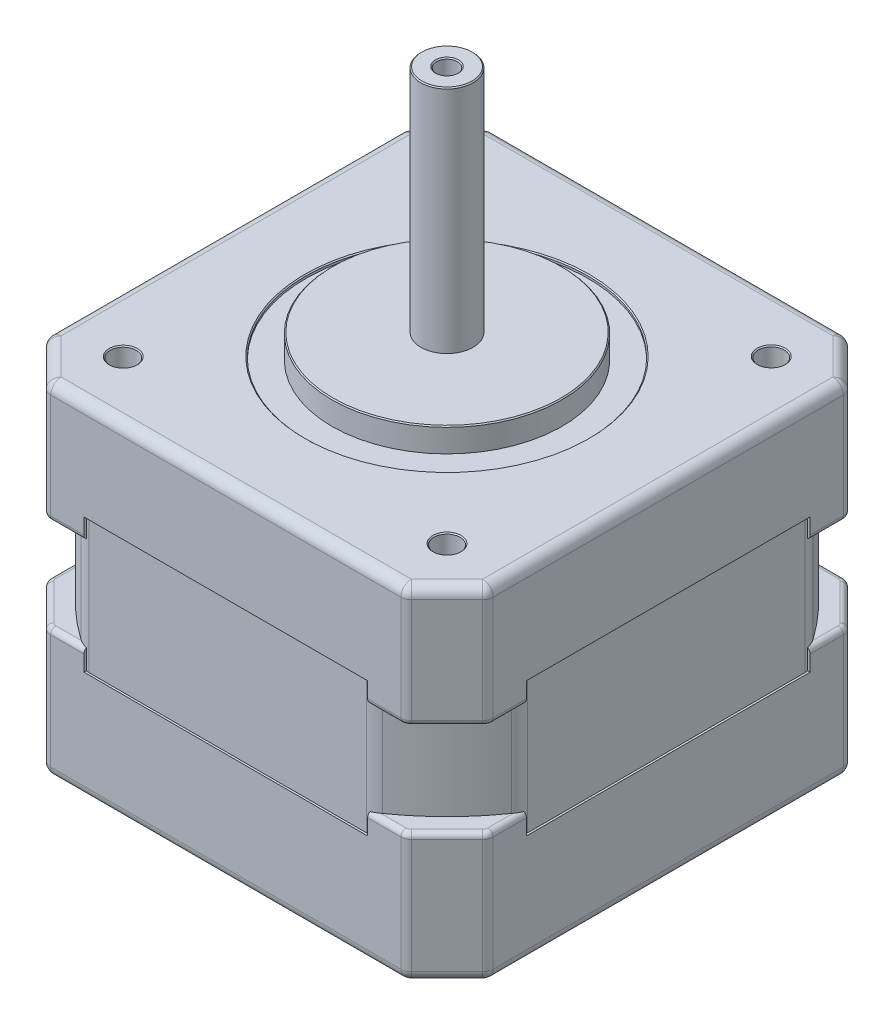
SolidWorks part; units mm, degrees
ref_plane "Front Plane" through (0, 0, 0) normal (0, 0, 1) x (1, 0, 0)
ref_plane "Top Plane" through (0, 0, 0) normal (0, 1, 0) x (1, 0, 0)
ref_plane "Right Plane" through (0, 0, 0) normal (1, 0, 0) x (0, 0, -1)
sketch "Sketch1" plane through (0, 0, 0) normal (0, 1, 0) x (1, 0, 0)
  line L0 (0, 21.15) -> (0, 0) construction
  line L1 (-21.15, 21.15) -> (-21.15, -21.15)
  line L2 (-21.15, -21.15) -> (21.15, -21.15)
  line L3 (-21.15, 21.15) -> (21.15, 21.15)
  line L4 (21.15, -21.15) -> (21.15, 21.15)
  line L5 (21.15, 0) -> (0, 0) construction
  line L6 (21.15, 21.15) -> (0, 0) construction
  circle A0 centre (15.5, 15.5) radius 1.25
  circle A1 centre (-15.4497, 15.5) radius 1.25
  circle A2 centre (-15.4497, -15.5) radius 1.25
  circle A3 centre (15.5, -15.5) radius 1.25
  dimension "D1" = 42.3
  dimension "D3" = 2.5
  dimension "D2" = 31
extrude "Boss-Extrude1" add sketch "Sketch1" against normal blind 32.8
chamfer "Chamfer1" distance 4 angle 45 4 edges at (21.15, -16.4, 21.15) (-21.15, -16.4, 21.15) (-21.15, -16.4, -21.15) (21.15, -16.4, -21.15)
sketch "Sketch2" plane through (0, 0, 0) normal (0, 1, 0) x (1, 0, 0)
  circle A0 centre (0, 0) radius 11
  dimension "D1" = 22
extrude "Boss-Extrude2" add sketch "Sketch2" along normal blind 2
sketch "Sketch6" plane through (0, -32.8, 0) normal (0, -1, 0) x (1, 0, 0)
  line L0 (-17.15, 21.15) -> (17.15, 21.15) construction
  line L1 (-21.15, -17.15) -> (-21.15, 17.15) construction
  line L2 (-17.15, 21.15) -> (-21.15, 17.15) construction
  line L3 (-17.15, 21.15) -> (-21.15, 17.15)
  line L4 (-21.15, 13.5626) -> (-21.15, 17.15)
  line L5 (-17.15, 21.15) -> (-13.5626, 21.15)
  arc A0 (-13.5626, 21.15) -> (-21.15, 13.5626) centre (0, 0) ccw
  dimension "D1" = 25.125
extrude "Cut-Extrude2" cut sketch "Sketch6" against normal offset from surface (8.85 mm away) 11.5 from offset 12.45 up to face at (0, 0, 0) offset against normal yes
pattern_circular "CirPattern1" count 4 over 360 about axis through (0, 10.7303, 0) along (0, -1, 0) of "Cut-Extrude2"
sketch "Sketch7" plane through (-21.15, 0, 0) normal (-1, 0, 0) x (0, 0, 1)
  line L0 (13.5626, -11.5) -> (13.5626, -20.35) construction
  line L1 (-13.5626, -9.5) -> (13.5626, -9.5)
  line L2 (-13.5626, -9.5) -> (-13.5626, -11.5)
  line L3 (-13.5626, -22.35) -> (13.5626, -22.35)
  line L4 (13.5626, -9.5) -> (13.5626, -11.5)
  line L5 (-13.5626, -11.5) -> (-13.5626, -20.35) construction
  line L6 (-17.15, -11.5) -> (-13.5626, -11.5) construction
  line L7 (-13.5626, -20.35) -> (-17.15, -20.35) construction
  line L8 (-21.15, -11.5) -> (-13.5626, -11.5) construction
  line L9 (-17.3563, -11.5) -> (-13.5626, -11.5)
  line L10 (-17.3563, -11.5) -> (-17.3563, -20.35)
  line L11 (-17.3563, -20.35) -> (-13.5626, -20.35)
  line L12 (19.15, -11.5) -> (19.15, -20.35)
  line L13 (21.15, -20.35) -> (17.15, -20.35) construction
  line L14 (13.5626, -11.5) -> (19.15, -11.5)
  line L15 (-13.5626, -20.35) -> (-13.5626, -22.35)
  line L16 (13.5626, -20.35) -> (13.5626, -22.35)
  line L17 (13.5626, -20.35) -> (19.15, -20.35)
  dimension "D1" = 2
  dimension "D2" = 2
extrude "Cut-Extrude3" cut sketch "Sketch7" against normal blind 0.2
pattern_circular "CirPattern2" count 4 over 360 about axis through (0, 2, 0) along (0, -1, 0) of "Cut-Extrude3"
sketch "Sketch3" plane through (0, 0, 0) normal (0, 1, 0) x (1, 0, 0)
  circle A0 centre (0, 0) radius 2.5
  dimension "D1" = 5
extrude "Boss-Extrude3" add sketch "Sketch3" along normal blind 24
sketch "Sketch8" plane through (0, -32.8, 0) normal (0, -1, 0) x (1, 0, 0)
  circle A0 centre (15.5, -15.5) radius 3.075
  circle A1 centre (15.5, 15.5) radius 3.075
  circle A2 centre (-15.4497, 15.5) radius 3.075
  circle A3 centre (-15.4497, -15.5) radius 3.075
  dimension "D1" = 6.15
extrude "Cut-Extrude4" cut sketch "Sketch8" against normal blind 2
sketch "Sketch9" plane through (0, -32.8, 0) normal (0, -1, 0) x (1, 0, 0)
  circle A0 centre (0, 0) radius 4.625
  dimension "D1" = 9.25
extrude "Cut-Extrude5" cut sketch "Sketch9" against normal blind 3
sketch "Sketch10" plane through (0, 0, -21.15) normal (0, 0, -1) x (-1, 0, 0)
  line L0 (-13.5626, -22.35) -> (13.5626, -22.35) construction
  line L1 (-4.1, -30.55) -> (4.1, -30.55)
  line L2 (-4.1, -30.55) -> (-4.1, -22.35)
  line L3 (-4.1, -22.35) -> (4.1, -22.35)
  line L4 (4.1, -30.55) -> (4.1, -22.35)
  line L5 (-4.1, -30.55) -> (4.1, -22.35) construction
  line L6 (-4.1, -22.35) -> (4.1, -30.55) construction
  line L7 (0, -11.5) -> (0, -20.35) construction
  point P0 (0, -26.45)
  dimension "D1" = 8.2
extrude "Cut-Extrude6" cut sketch "Sketch10" against normal blind 0.5
sketch "Sketch11" plane through (0, 0, 0) normal (0, 1, 0) x (1, 0, 0)
  circle A0 centre (0, 0) radius 11 construction
  circle A1 centre (0, 0) radius 11
  circle A2 centre (0, 0) radius 13.5
  dimension "D1" = 2.5
extrude "Cut-Extrude7" cut sketch "Sketch11" against normal blind 0.3
fillet "Fillet2" radius 2 8 edges at (-13.8695, -15.925, -20.95) (13.8695, -15.925, -20.95) (20.95, -15.925, -13.8695) (20.95, -15.925, 13.8695) (13.8695, -15.925, 20.95) (-13.8695, -15.925, 20.95) (-20.95, -15.925, 13.8695) (-20.95, -15.925, -13.8695)
fillet "Fillet1" radius 1 32 edges at (0, 0, 21.15) (0, -32.8, 21.15) (19.15, 0, -19.15) (19.15, -32.8, -19.15) (17.15, -5.75, -21.15) (17.15, -26.575, -21.15) (0, 0, -21.15) (0, -32.8, -21.15) (-17.15, -5.75, -21.15) (-17.15, -26.575, -21.15) (-19.15, 0, -19.15) (-19.15, -32.8, -19.15) (-21.15, -5.75, -17.15) (-21.15, -26.575, -17.15) (-21.15, 0, 0) (-21.15, -32.8, 0) (-21.15, -5.75, 17.15) (-21.15, -26.575, 17.15) (-19.15, 0, 19.15) (-17.15, -5.75, 21.15) (-17.15, -26.575, 21.15) (-19.15, -32.8, 19.15) (21.15, -5.75, -17.15) (21.15, -26.575, -17.15) (21.15, -32.8, 0) (21.15, 0, 0) (17.15, -5.75, 21.15) (17.15, -26.575, 21.15) (19.15, 0, 19.15) (21.15, -5.75, 17.15) (21.15, -26.575, 17.15) (19.15, -32.8, 19.15)
fillet "Fillet3" radius 0.5 40 edges at (21.15, -11.5, -15.1492) (21.0739, -11.5, -17.1185) (15.1492, -11.5, -21.15) (17.1185, -11.5, -21.0739) (15.1492, -20.35, -21.15) (17.1185, -20.35, -21.0739) (19.15, -20.35, -19.15) (21.0739, -20.35, -17.1185) (15.1492, -11.5, 21.15) (17.1185, -11.5, 21.0739) (21.15, -11.5, 15.1492) (21.0739, -11.5, 17.1185) (21.15, -20.35, 15.1492) (21.0739, -20.35, 17.1185) (15.1492, -20.35, 21.15) (17.1185, -20.35, 21.0739) (-21.15, -20.35, -15.1492) (-21.0739, -20.35, -17.1185) (-15.1492, -20.35, -21.15) (-17.1185, -20.35, -21.0739) (-15.1492, -20.35, 21.15) (-17.1185, -20.35, 21.0739) (-21.15, -20.35, 15.1492) (-21.0739, -20.35, 17.1185) (-21.15, -11.5, 15.1492) (-21.0739, -11.5, 17.1185) (-15.1492, -11.5, 21.15) (-17.1185, -11.5, 21.0739) (-15.1492, -11.5, -21.15) (-17.1185, -11.5, -21.0739) (-21.15, -11.5, -15.1492) (-21.0739, -11.5, -17.1185) (19.15, -11.5, -19.15) (21.15, -20.35, -15.1492) (19.15, -11.5, 19.15) (19.15, -20.35, 19.15) (-19.15, -20.35, -19.15) (-19.15, -20.35, 19.15) (-19.15, -11.5, 19.15) (-19.15, -11.5, -19.15)
chamfer "Chamfer2" distance 0.1 angle 45 6 edges at (0, 2, 11) (0, 0, 13.5) (-15.4497, 0, 16.75) (-15.4497, 0, -14.25) (15.5, 0, -14.25) (15.5, 0, 16.75)
sketch "Sketch12" plane through (0, 24, 0) normal (0, 1, 0) x (1, 0, 0)
  circle A0 centre (0, 0) radius 1
  dimension "D1" = 2
extrude "Cut-Extrude8" cut sketch "Sketch12" against normal blind 2.5
chamfer "Chamfer3" distance 0.1 angle 45 2 edges at (0, 24, 2.5) (0, 24, 1)
chamfer "Chamfer4" distance 0.3 angle 45 5 edges at (15.5, -32.8, -18.575) (15.5, -32.8, 12.425) (-15.4497, -32.8, 12.425) (-15.4497, -32.8, -18.575) (0, -32.8, -4.625)
sketch "Sketch13" plane through (0, 0, -20.65) normal (0, 0, -1) x (-1, 0, 0)
  line L0 (-2.025, -29.05) -> (2.025, -29.05) construction
  line L4 (-4.1, -30.55) -> (4.1, -30.55) construction
  line L8 (0, -29.8) -> (0, -32.5) construction
  circle A0 centre (-2.025, -29.05) radius 0.65
  circle A1 centre (-0.675, -29.05) radius 0.65
  circle A2 centre (0.675, -29.05) radius 0.65
  circle A3 centre (2.025, -29.05) radius 0.65
  point P8 (0, -29.05)
  dimension "D1" = 1.3
  dimension "D3" = 1.35
  dimension "D2" = 1.5
  dimension "D4" = 1.35
  dimension "D5" = 1.35
extrude "Boss-Extrude5" add sketch "Sketch13" along normal blind 5.5
sketch "Sketch5" plane through (-12.85, -32.8, 0) normal (0, 1, 0) x (0, 0, -1)
  line L0 (-20.15, -7.0234) -> (20.15, -7.0234) construction
  line L1 (20.15, 3.8858) -> (20.15, -29.5858) construction
  line L2 (-20.15, -29.5858) -> (-20.15, 3.8858) construction
  text T0 "http://multilogica-shop.com\r\nMOTOR\r\nPASSO A PASSO\r\nCód:MOT0030033\r\n" font "Century Gothic" height 1.5
extrude "Cut-Extrude1" cut sketch "Sketch5" along normal blind 0.3
ref_plane "Plane1" through (0, 10, 0) normal (0, 1, 0) x (1, 0, 0)
sketch "Sketch14" plane through (0, 10, 0) normal (0, 1, 0) x (1, 0, 0)
  line L0 (-16.7358, 21.15) -> (16.7358, 21.15) construction
  line L1 (-27.5, 21.15) -> (27.5, 21.15)
  line L2 (-27.5, 21.15) -> (-27.5, 6)
  line L3 (27.5, 21.15) -> (27.5, 6)
  line L4 (0, 0) -> (0, 29.0694) construction
  line L5 (27.5, 6) -> (12.0934, 6)
  line L6 (-12.0934, 6) -> (-27.5, 6)
  circle A0 centre (15.5, 15.5) radius 1.25 construction
  circle A1 centre (-15.4497, 15.5) radius 1.25 construction
  circle A2 centre (0, 0) radius 13.5 construction
  circle A3 centre (15.5, 15.5) radius 1.25
  circle A4 centre (-15.4497, 15.5) radius 1.25
  arc A5 (12.0934, 6) -> (-12.0934, 6) centre (0, 0) ccw
  point P16 (0, 21.15)
  dimension "D1" = 15.15
  dimension "D2" = 27.5
  dimension "D3" = 55
equation "\"D2@Sketch7\"=\"D1@Sketch7\""
